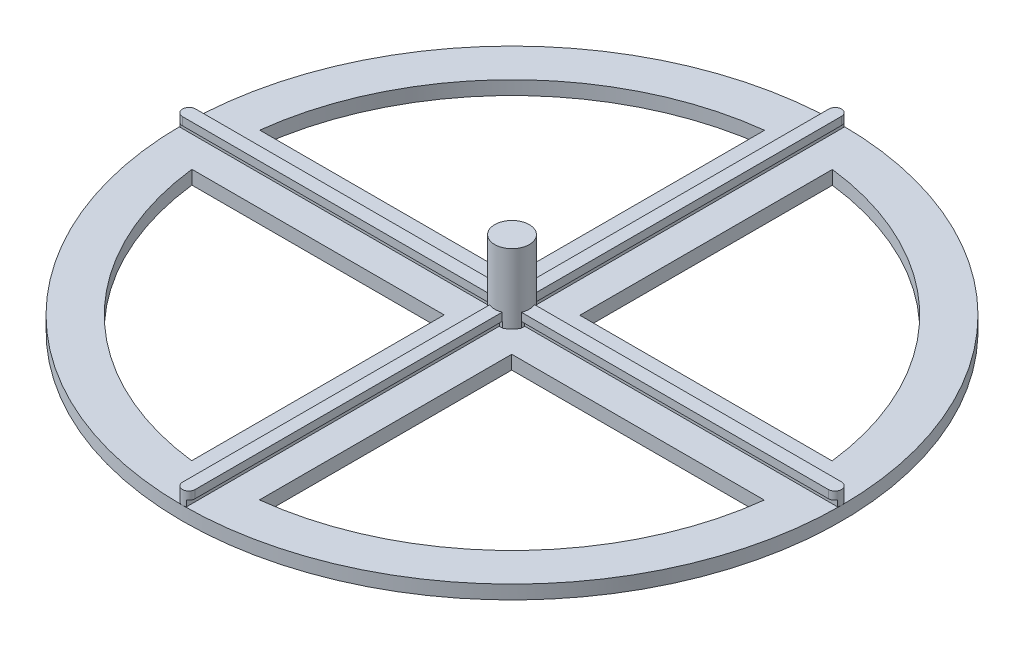
SolidWorks part; units mm, degrees
ref_plane "Front Plane" through (0, 0, 0) normal (0, 0, 1) x (1, 0, 0)
ref_plane "Top Plane" through (0, 0, 0) normal (0, 1, 0) x (1, 0, 0)
ref_plane "Right Plane" through (0, 0, 0) normal (1, 0, 0) x (0, 0, -1)
sketch "Sketch1" plane through (0, 0, 0) normal (0, 1, 0) x (1, 0, 0)
  circle A0 centre (0, 0) radius 76.2
  dimension "D1" = 152.4
extrude "Boss-Extrude1" add sketch "Sketch1" along normal blind 3.175
sketch "Sketch2" plane through (0, 3.175, 0) normal (0, 1, 0) x (1, 0, 0)
  line L0 (0, -76.2) -> (0, 76.2)
  line L1 (-76.2, 0) -> (76.2, 0)
  line L2 (-74.676, 0) -> (74.676, 0) construction
  line L3 (-74.676, 1.524) -> (74.676, 1.524)
  line L4 (-74.676, -1.524) -> (74.676, -1.524)
  line L5 (0, 74.7395) -> (0, -74.7395) construction
  line L6 (1.4605, 74.7395) -> (1.4605, -74.7395)
  line L7 (-1.4605, 74.7395) -> (-1.4605, -74.7395)
  circle A0 centre (0, 0) radius 76.2 construction
  arc A1 (-74.676, 1.524) -> (-74.676, -1.524) centre (-74.676, 0) ccw
  arc A2 (74.676, -1.524) -> (74.676, 1.524) centre (74.676, 0) ccw
  arc A3 (1.4605, 74.7395) -> (-1.4605, 74.7395) centre (0, 74.7395) ccw
  arc A4 (-1.4605, -74.7395) -> (1.4605, -74.7395) centre (0, -74.7395) ccw
  point P7 (0, 0)
  point P11 (0, 0)
  point P12 (0, 0)
  point P19 (0, 0)
  dimension "D1" = 3.048
  dimension "D2" = 2.921
extrude "Boss-Extrude2" add sketch "Sketch2" along normal blind 3.175 contours L7 A4 L6 A3 | L4 A1 L3 A2
sketch "Sketch3" plane through (0, 6.35, 0) normal (0, 1, 0) x (1, 0, 0)
  circle A0 centre (0, 0) radius 4
  dimension "D1" = 8
extrude "Boss-Extrude3" add sketch "Sketch3" along normal blind 12.954 and the other way up to surface (3.175 mm away) other way up to face at (34.0393, 3.175, -34.0774)
sketch "Sketch4" plane through (0, 3.175, 0) normal (0, 1, 0) x (1, 0, 0)
  line L0 (-7.8105, 7.874) -> (-39.5605, 7.874)
  line L1 (-74.676, 1.524) -> (-3.6983, 1.524) construction
  line L2 (-1.4605, 74.7395) -> (-1.4605, 3.7238) construction
  line L3 (-7.8105, 7.874) -> (-7.8105, 63.0178)
  line L4 (-39.5605, 7.874) -> (-63.0099, 7.874)
  line L5 (-7.8105, 63.0178) -> (-7.8105, 66.2159)
  line L6 (-63.0099, 7.874) -> (-66.2084, 7.874)
  line L7 (7.874, 63.0099) -> (7.874, 66.2084)
  line L8 (7.874, 39.5605) -> (7.874, 63.0099)
  line L9 (7.874, 7.8105) -> (7.874, 39.5605)
  line L10 (7.874, 7.8105) -> (63.0178, 7.8105)
  line L11 (63.0178, 7.8105) -> (66.2159, 7.8105)
  line L12 (63.0099, -7.874) -> (66.2084, -7.874)
  line L13 (39.5605, -7.874) -> (63.0099, -7.874)
  line L14 (7.8105, -7.874) -> (39.5605, -7.874)
  line L15 (7.8105, -7.874) -> (7.8105, -63.0178)
  line L16 (7.8105, -63.0178) -> (7.8105, -66.2159)
  line L17 (-7.874, -63.0099) -> (-7.874, -66.2084)
  line L18 (-7.874, -39.5605) -> (-7.874, -63.0099)
  line L19 (-7.874, -7.8105) -> (-7.874, -39.5605)
  line L20 (-7.874, -7.8105) -> (-63.0178, -7.8105)
  line L21 (-63.0178, -7.8105) -> (-66.2159, -7.8105)
  arc A2 (-7.8105, 66.2159) -> (-66.2084, 7.874) centre (0, 0) ccw
  arc A3 (66.2159, 7.8105) -> (7.874, 66.2084) centre (0, 0) ccw
  arc A4 (7.8105, -66.2159) -> (66.2084, -7.874) centre (0, 0) ccw
  arc A5 (-66.2159, -7.8105) -> (-7.874, -66.2084) centre (0, 0) ccw
  point P34 (0, 0)
  dimension "D1" = 6.35
  dimension "D3" = 4
  dimension "D2" = 6.35
extrude "Cut-Extrude1" cut sketch "Sketch4" against normal through all
sketch "Sketch6" plane through (0, 0, 1.524) normal (0, 0, 1) x (1, 0, 0)
  line L0 (3.6983, 3.175) -> (3.6983, 4.5085)
  line L1 (3.6983, 6.35) -> (3.6983, 3.175) construction
  line L2 (3.6983, 4.5085) -> (76.2, 4.5085)
  line L3 (76.2, 3.175) -> (76.2, 6.35) construction
  line L4 (76.2, 4.5085) -> (76.2, 3.175)
  line L5 (76.2, 3.175) -> (3.6983, 3.175)
extrude "Cut-Extrude3" cut sketch "Sketch6" against normal blind 0.762
pattern_circular "CirPattern1" count 4 over 360 about axis through (0, 19.304, 0) along (0, 1, 0) of "Cut-Extrude3"
sketch "Sketch7" plane through (0, 0, -1.524) normal (0, 0, -1) x (-1, 0, 0)
  line L0 (-3.6983, 3.175) -> (-3.6983, 4.5085)
  line L1 (-3.6983, 6.35) -> (-3.6983, 3.175) construction
  line L2 (-3.6983, 4.5085) -> (-77.7609, 4.5085)
  line L3 (-77.7609, 4.5085) -> (-77.7609, 3.175)
  line L4 (-77.7609, 3.175) -> (-3.6983, 3.175)
extrude "Cut-Extrude4" cut sketch "Sketch7" against normal blind 0.762
pattern_circular "CirPattern2" count 4 over 360 about axis through (0, 19.304, 0) along (0, 1, 0) of "Cut-Extrude4"
